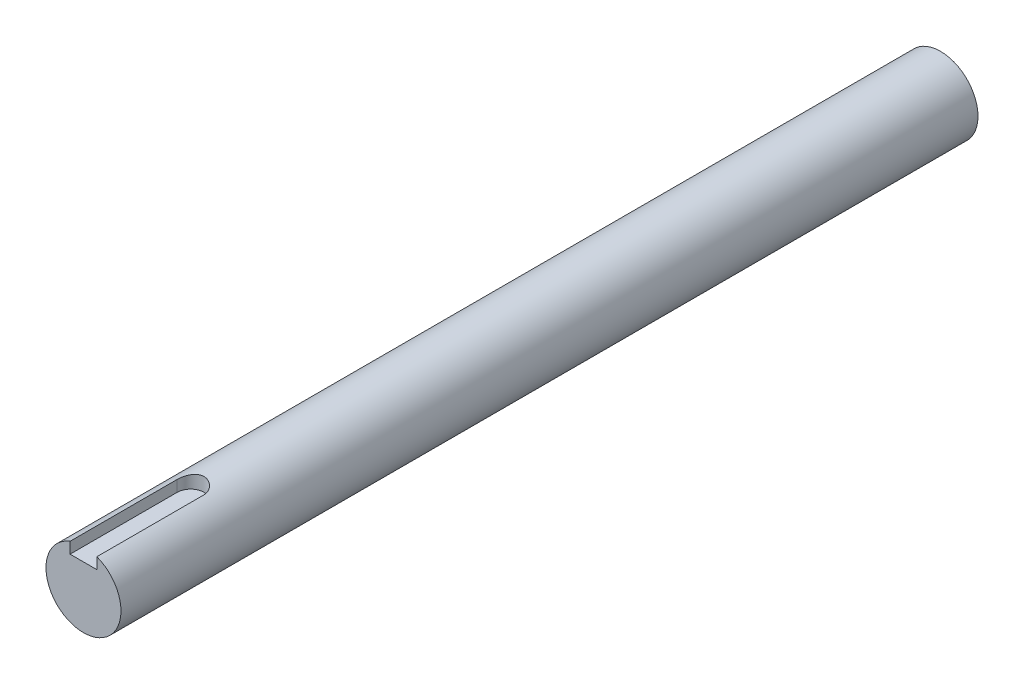
SolidWorks part; units mm, degrees
ref_plane "Front Plane" through (0, 0, 0) normal (0, 0, 1) x (1, 0, 0)
ref_plane "Top Plane" through (0, 0, 0) normal (0, 1, 0) x (1, 0, 0)
ref_plane "Right Plane" through (0, 0, 0) normal (1, 0, 0) x (0, 0, -1)
sketch "Esquisse1" plane through (0, 0, 0) normal (0, 0, 1) x (1, 0, 0)
  circle A0 centre (0, 0) radius 7
  dimension "D1" = 14
extrude "Boss.-Extru.1" add sketch "Esquisse1" along normal blind 160
sketch "Esquisse2" plane through (0, 0, 0) normal (0, 0, -1) x (-1, 0, 0)
  circle A0 centre (0, 0) radius 4.1881
extrude "Enlèv. mat.-Extru.1" cut sketch "Esquisse2" against normal blind 20
sketch3d "Esquisse3D1"
  point P0 (-2.2929, 6.6138, 126.9082)
sketch3d "Esquisse3D2"
  point P0 (0.8674, 6.946, 78.9653)
ref_plane "Plan2" through (0, 6.946, 0) normal (0, -1, 0) x (1, 0, 0)
sketch "Esquisse3" plane through (0, 6.946, 0) normal (0, -1, 0) x (1, 0, 0)
  line L0 (0, 160) -> (0, 140) construction
  line L1 (2.5, 160) -> (2.5, 140)
  line L2 (-2.5, 160) -> (-2.5, 140)
  line L3 (7, 160) -> (-7, 160) construction
  arc A0 (2.5, 160) -> (-2.5, 160) centre (0, 160) ccw
  arc A1 (-2.5, 140) -> (2.5, 140) centre (0, 140) ccw
  point P3 (0, 150)
  point P8 (-2.5, 150)
  point P9 (2.5, 150)
  dimension "D1" = 5
  dimension "D2" = 20
  dimension "D3" = 20
extrude "Enlèv. mat.-Extru.2" cut sketch "Esquisse3" along normal blind 2.5 and the other way blind 2.5
